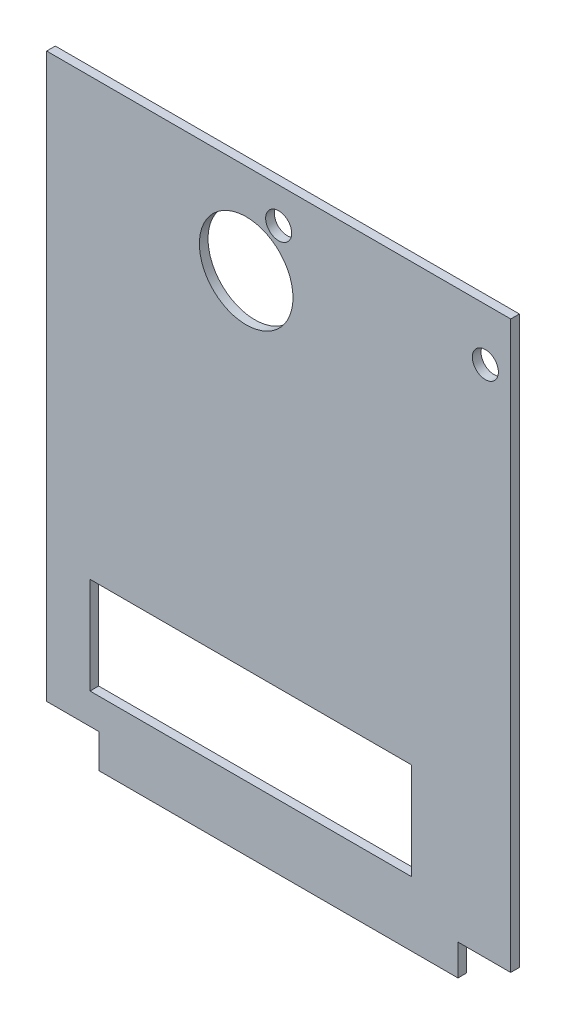
SolidWorks part; units mm, degrees
ref_plane "Front Plane" through (0, 0, 0) normal (0, 0, 1) x (1, 0, 0)
ref_plane "Top Plane" through (0, 0, 0) normal (0, 1, 0) x (1, 0, 0)
ref_plane "Right Plane" through (0, 0, 0) normal (1, 0, 0) x (0, 0, -1)
sketch "Sketch1" plane through (0, 0, 0) normal (0, 0, 1) x (1, 0, 0)
  line L1 (-42.814, 46.3633) -> (38.72, 46.3633)
  line L2 (-42.814, 46.3633) -> (-42.814, -58.5387)
  line L3 (-42.814, -58.5387) -> (38.72, -58.5387)
  line L4 (38.72, 46.3633) -> (38.72, -58.5387)
  dimension "D1" = 104.902
  dimension "D2" = 81.534
extrude "Boss-Extrude1" add sketch "Sketch1" along normal blind 1.524
sketch "Sketch2" plane through (0, 0, 1.524) normal (0, 0, 1) x (1, 0, 0)
  line L1 (-42.814, -58.5387) -> (-33.644, -58.5387)
  line L2 (-42.814, -58.5387) -> (-42.814, -52.5887)
  line L3 (-42.814, -52.5887) -> (-33.644, -52.5887)
  line L4 (-33.644, -58.5387) -> (-33.644, -52.5887)
  line L5 (38.72, -58.5387) -> (29.4539, -58.5387)
  line L6 (38.72, -58.5387) -> (38.72, -53.0667)
  line L7 (38.72, -53.0667) -> (29.4539, -53.0667)
  line L8 (29.4539, -58.5387) -> (29.4539, -53.0667)
  dimension "D1" = 9.17
  dimension "D2" = 5.95
extrude "Cut-Extrude1" cut sketch "Sketch2" against normal blind 1.524
sketch "Sketch4" plane through (0, 0, 1.524) normal (0, 0, 1) x (1, 0, 0)
  line L4 (-35.184, -47.1987) -> (21.316, -47.1987)
  line L5 (-35.184, -47.1987) -> (-35.184, -30.1987)
  line L6 (-35.184, -30.1987) -> (21.316, -30.1987)
  line L7 (21.316, -47.1987) -> (21.316, -30.1987)
  dimension "D3" = 17
  dimension "D4" = 56.5
extrude "Cut-Extrude2" cut sketch "Sketch4" against normal blind 1.524
sketch "Sketch6" plane through (0, 0, 1.524) normal (0, 0, 1) x (1, 0, 0)
  line L0 (38.72, 46.3633) -> (36.55, 46.3633)
  line L2 (38.72, 46.3633) -> (-42.814, 46.3633) construction
  circle A0 centre (-2.047, 40.1583) radius 2.285
  circle A1 centre (34.265, 37.1933) radius 2.285
  dimension "D2" = 4.57
extrude "Cut-Extrude3" cut sketch "Sketch6" against normal blind 1.524 contours A0 | A1 region at (-2.047, 40.1583, 1.524) region at (34.265, 37.1933, 1.524)
sketch "Sketch8" plane through (0, 0, 1.524) normal (0, 0, 1) x (1, 0, 0)
  circle A0 centre (-7.7531, 30.4572) radius 8.2241
extrude "Cut-Extrude4" cut sketch "Sketch8" against normal blind 2.54
